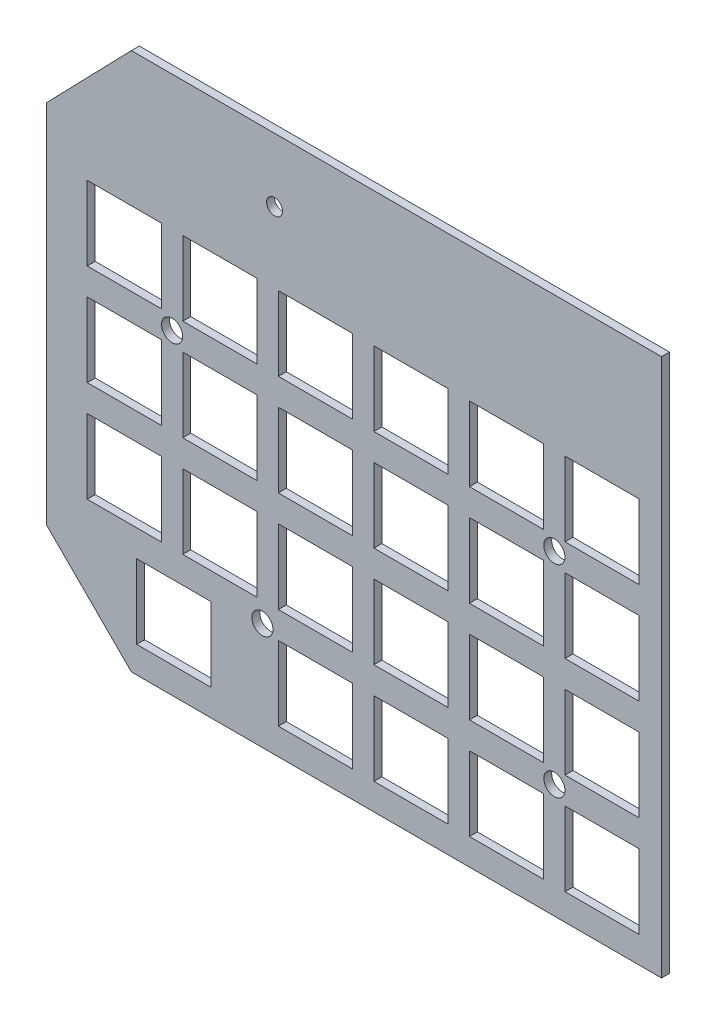
SolidWorks part; units mm, degrees
ref_plane "Plan de face" through (0, 0, 0) normal (0, 0, 1) x (1, 0, 0)
ref_plane "Plan de dessus" through (0, 0, 0) normal (0, 1, 0) x (1, 0, 0)
ref_plane "Plan de droite" through (0, 0, 0) normal (1, 0, 0) x (0, 0, -1)
sketch "Esquisse1" plane through (0, 0, 0) normal (0, 0, 1) x (1, 0, 0)
  line L0 (0, -85) -> (16, -101)
  line L4 (116, 0.5) -> (116, -101)
  line L5 (16, 0.5) -> (0, -16)
  line L7 (116, 0.5) -> (16, 0.5)
  line L8 (0, -16) -> (0, -85)
  line L9 (16, -101) -> (116, -101)
  dimension "D1" = 101.5
  dimension "D2" = 116
  dimension "D3" = 16
  dimension "D4" = 16
  dimension "D5" = 16
  dimension "D6" = 16
extrude "Boss.-Extru.1" add sketch "Esquisse1" along normal blind 1.5
sketch "Esquisse3" plane through (0, 0, 0) normal (0, 0, -1) x (-1, 0, 0)
  line L0 (-93.7743, -24.85) -> (-93.7743, -38.85)
  line L1 (-111.8, -24.85) -> (-97.8, -24.85)
  line L2 (-111.8, -24.85) -> (-111.8, -38.85)
  line L3 (-111.8, -38.85) -> (-97.8, -38.85)
  line L4 (-97.8, -24.85) -> (-97.8, -38.85)
  line L5 (-104.8, -38.85) -> (-104.8, -24.85) construction
  line L6 (-111.8, -31.85) -> (-97.8, -31.85) construction
  line L7 (-93.7743, -24.85) -> (-79.7743, -24.85)
  line L8 (-79.7743, -24.85) -> (-79.7743, -38.85)
  line L9 (-93.7743, -38.85) -> (-79.7743, -38.85)
  line L10 (-75.7486, -24.85) -> (-75.7486, -38.85)
  line L11 (-75.7486, -24.85) -> (-61.7486, -24.85)
  line L12 (-61.7486, -24.85) -> (-61.7486, -38.85)
  line L13 (-75.7486, -38.85) -> (-61.7486, -38.85)
  line L14 (-57.7229, -24.85) -> (-57.7229, -38.85)
  line L15 (-57.7229, -24.85) -> (-43.7229, -24.85)
  line L16 (-43.7229, -24.85) -> (-43.7229, -38.85)
  line L17 (-57.7229, -38.85) -> (-43.7229, -38.85)
  line L18 (-39.6973, -24.85) -> (-39.6973, -38.85)
  line L19 (-39.6973, -24.85) -> (-25.6973, -24.85)
  line L20 (-25.6973, -24.85) -> (-25.6973, -38.85)
  line L21 (-39.6973, -38.85) -> (-25.6973, -38.85)
  line L22 (-21.6716, -24.85) -> (-21.6716, -38.85)
  line L23 (-21.6716, -24.85) -> (-7.6716, -24.85)
  line L24 (-7.6716, -24.85) -> (-7.6716, -38.85)
  line L25 (-21.6716, -38.85) -> (-7.6716, -38.85)
  line L26 (-93.7743, -43.9) -> (-93.7743, -57.9)
  line L27 (-93.7743, -43.9) -> (-79.7743, -43.9)
  line L28 (-79.7743, -43.9) -> (-79.7743, -57.9)
  line L29 (-93.7743, -57.9) -> (-79.7743, -57.9)
  line L30 (-75.7486, -43.9) -> (-75.7486, -57.9)
  line L31 (-75.7486, -43.9) -> (-61.7486, -43.9)
  line L32 (-61.7486, -43.9) -> (-61.7486, -57.9)
  line L33 (-75.7486, -57.9) -> (-61.7486, -57.9)
  line L34 (-57.7229, -43.9) -> (-57.7229, -57.9)
  line L35 (-57.7229, -43.9) -> (-43.7229, -43.9)
  line L36 (-43.7229, -43.9) -> (-43.7229, -57.9)
  line L37 (-57.7229, -57.9) -> (-43.7229, -57.9)
  line L38 (-39.6973, -43.9) -> (-39.6973, -57.9)
  line L39 (-39.6973, -43.9) -> (-25.6973, -43.9)
  line L40 (-25.6973, -43.9) -> (-25.6973, -57.9)
  line L41 (-39.6973, -57.9) -> (-25.6973, -57.9)
  line L42 (-21.6716, -43.9) -> (-21.6716, -57.9)
  line L43 (-21.6716, -43.9) -> (-7.6716, -43.9)
  line L44 (-7.6716, -43.9) -> (-7.6716, -57.9)
  line L45 (-21.6716, -57.9) -> (-7.6716, -57.9)
  line L46 (-93.7743, -62.95) -> (-93.7743, -76.95)
  line L47 (-93.7743, -62.95) -> (-79.7743, -62.95)
  line L48 (-79.7743, -62.95) -> (-79.7743, -76.95)
  line L49 (-93.7743, -76.95) -> (-79.7743, -76.95)
  line L50 (-75.7486, -62.95) -> (-75.7486, -76.95)
  line L51 (-75.7486, -62.95) -> (-61.7486, -62.95)
  line L52 (-61.7486, -62.95) -> (-61.7486, -76.95)
  line L53 (-75.7486, -76.95) -> (-61.7486, -76.95)
  line L54 (-57.7229, -62.95) -> (-57.7229, -76.95)
  line L55 (-57.7229, -62.95) -> (-43.7229, -62.95)
  line L56 (-43.7229, -62.95) -> (-43.7229, -76.95)
  line L57 (-57.7229, -76.95) -> (-43.7229, -76.95)
  line L58 (-39.6973, -62.95) -> (-39.6973, -76.95)
  line L59 (-39.6973, -62.95) -> (-25.6973, -62.95)
  line L60 (-25.6973, -62.95) -> (-25.6973, -76.95)
  line L61 (-39.6973, -76.95) -> (-25.6973, -76.95)
  line L62 (-21.6716, -62.95) -> (-21.6716, -76.95)
  line L63 (-21.6716, -62.95) -> (-7.6716, -62.95)
  line L64 (-7.6716, -62.95) -> (-7.6716, -76.95)
  line L65 (-21.6716, -76.95) -> (-7.6716, -76.95)
  line L66 (-93.7743, -82) -> (-93.7743, -96)
  line L67 (-93.7743, -82) -> (-79.7743, -82)
  line L68 (-79.7743, -82) -> (-79.7743, -96)
  line L69 (-93.7743, -96) -> (-79.7743, -96)
  line L70 (-75.7486, -82) -> (-75.7486, -96)
  line L71 (-75.7486, -82) -> (-61.7486, -82)
  line L72 (-61.7486, -82) -> (-61.7486, -96)
  line L73 (-75.7486, -96) -> (-61.7486, -96)
  line L74 (-57.7229, -82) -> (-57.7229, -96)
  line L75 (-57.7229, -82) -> (-43.7229, -82)
  line L76 (-43.7229, -82) -> (-43.7229, -96)
  line L77 (-57.7229, -96) -> (-43.7229, -96)
  line L86 (-111.8, -43.9) -> (-111.8, -57.9)
  line L87 (-111.8, -43.9) -> (-97.8, -43.9)
  line L88 (-97.8, -43.9) -> (-97.8, -57.9)
  line L89 (-111.8, -57.9) -> (-97.8, -57.9)
  line L90 (-111.8, -62.95) -> (-111.8, -76.95)
  line L91 (-111.8, -62.95) -> (-97.8, -62.95)
  line L92 (-97.8, -62.95) -> (-97.8, -76.95)
  line L93 (-111.8, -76.95) -> (-97.8, -76.95)
  line L94 (-111.8, -82) -> (-111.8, -96)
  line L95 (-111.8, -82) -> (-97.8, -82)
  line L96 (-97.8, -82) -> (-97.8, -96)
  line L97 (-111.8, -96) -> (-97.8, -96)
  line L98 (-7.6716, -82) -> (-7.6716, -96) [skipped]
  line L99 (-21.6716, -96) -> (-7.6716, -96) [skipped]
  line L100 (-21.6716, -82) -> (-21.6716, -96) [skipped]
  line L101 (-21.6716, -82) -> (-7.6716, -82) [skipped]
  line L102 (-93.7743, -82) -> (-97.8, -76.95) construction
  line L103 (-116, -101) -> (-116, 0.5) construction
  line L104 (-16, -101) -> (-116, -101) construction
  line L107 (-39.6973, -82) -> (-25.6973, -82) [skipped]
  line L108 (-25.6973, -82) -> (-25.6973, -96) [skipped]
  line L109 (-39.6973, -82) -> (-39.6973, -96) [skipped]
  line L110 (-39.6973, -96) -> (-25.6973, -96) [skipped]
  line L111 (0, -16) -> (0, -85) construction
  line L112 (-31, -82) -> (-17, -82)
  line L113 (-31, -82) -> (-31, -96)
  line L114 (-31, -96) -> (-17, -96)
  line L115 (-17, -82) -> (-17, -96)
  line L116 (-24, -96) -> (-24, -82) construction
  line L117 (-31, -89) -> (-17, -89) construction
  line L118 (-97.8, -38.85) -> (-93.7743, -43.9) construction
  line L119 (-25.6973, -38.85) -> (-21.6716, -43.9) construction
  line L120 (-43.7229, -76.95) -> (-37.7098, -84.4932) construction
  line L122 (-116, 0.5) -> (-16, 0.5) construction
  circle A0 centre (-95.7872, -41.375) radius 2
  circle A1 centre (-23.6844, -41.375) radius 2
  circle A2 centre (-40.7164, -80.7216) radius 2
  circle A3 centre (-95.7872, -79.475) radius 2
  circle A5 centre (-43, -11.5) radius 1.5
  point P0 (-104.8, -31.85)
  point P84 (-24, -89)
  dimension "D7" = 43
  dimension "D8" = 12
  dimension "D1" = 14
  dimension "D2" = 14
  dimension "D5" = 5
  dimension "D6" = 4.2
  dimension "D10" = 14
  dimension "D11" = 14
  dimension "D12" = 17
  dimension "D3" = 6
  dimension "D4" = 4
extrude "Enlèv. mat.-Extru.2" cut sketch "Esquisse3" against normal blind 10
